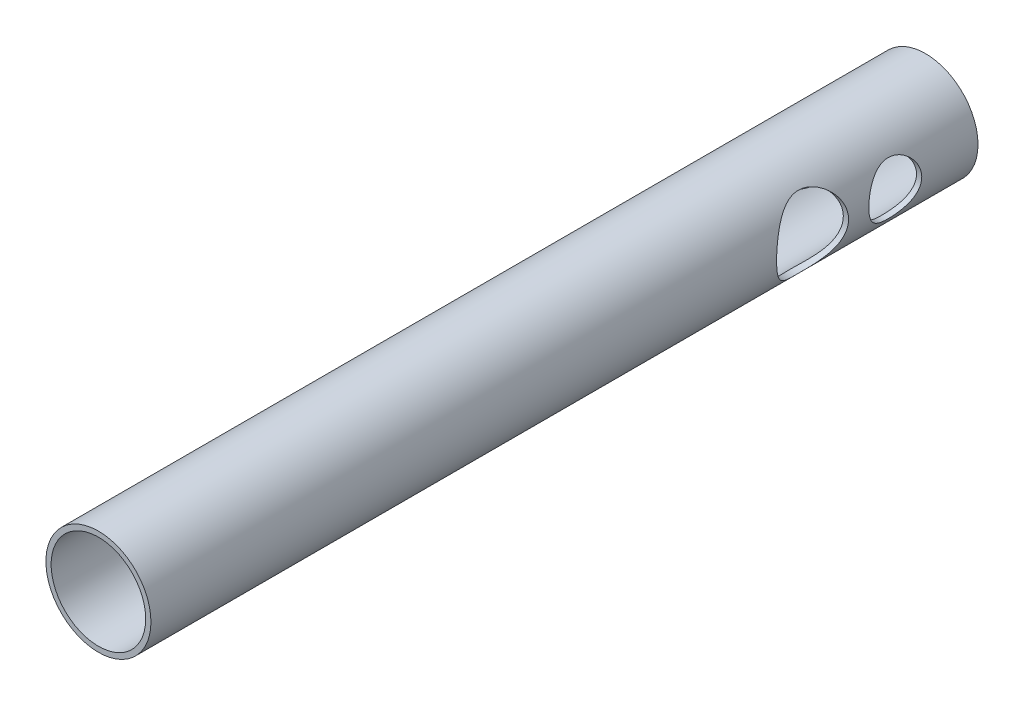
SolidWorks part; units mm, degrees
ref_plane "Front Plane" through (0, 0, 0) normal (0, 0, 1) x (1, 0, 0)
ref_plane "Top Plane" through (0, 0, 0) normal (0, 1, 0) x (1, 0, 0)
ref_plane "Right Plane" through (0, 0, 0) normal (1, 0, 0) x (0, 0, -1)
sketch "Sketch1" plane through (0, 0, 0) normal (0, 0, 1) x (1, 0, 0)
  circle A0 centre (0, 0) radius 31.75
  circle A1 centre (0, 0) radius 28.575
  dimension "D1" = 63.5
  dimension "D2" = 57.15
extrude "Boss-Extrude1" add sketch "Sketch1" along normal blind 250 and the other way blind 250 contours A1 | A0 region at (0, 0, 0)
sketch "Sketch2" plane through (0, 0, 0) normal (1, 0, 0) x (0, 0, -1)
  circle A0 centre (200, 0) radius 21.75
  circle A1 centre (150, 0) radius 16
  dimension "D1" = 32
  dimension "D2" = 43.5
  dimension "D3" = 200
  dimension "D4" = 150
extrude "Cut-Extrude1" cut sketch "Sketch2" against normal through all
sketch "Sketch3" plane through (0, 0, 0) normal (1, 0, 0) x (0, 0, -1)
  circle A0 centre (200, 0) radius 16
  circle A1 centre (150, 0) radius 21.75
  dimension "D1" = 43.5
  dimension "D2" = 32
  dimension "D3" = 150
  dimension "D4" = 200
extrude "Cut-Extrude2" cut sketch "Sketch3" along normal through all
